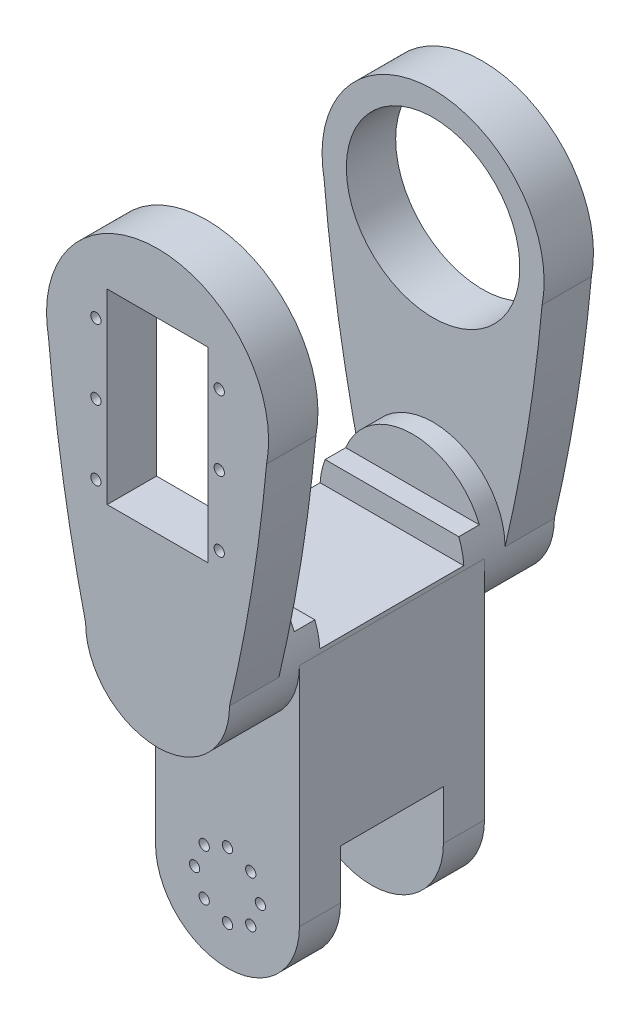
SolidWorks part; units mm, degrees
ref_plane "Front Plane" through (0, 0, 0) normal (0, 0, 1) x (1, 0, 0)
ref_plane "Top Plane" through (0, 0, 0) normal (0, 1, 0) x (1, 0, 0)
ref_plane "Right Plane" through (0, 0, 0) normal (1, 0, 0) x (0, 0, -1)
sketch "Sketch2" plane through (0, 0, 0) normal (0, 0, 1) x (1, 0, 0)
  line L0 (-17.5, -27.5) -> (17.5, -27.5)
  line L1 (17.5, -27.5) -> (-17.5, -27.5)
  line L2 (17.5, -27.5) -> (17.5, 27.5)
  line L3 (17.5, 27.5) -> (-17.5, 27.5)
  line L4 (-17.5, -27.5) -> (-17.5, 27.5)
  line L5 (0, 27.5) -> (0, -27.5) construction
  line L6 (17.5, 0) -> (-17.5, 0) construction
  arc A0 (17.5, -27.5) -> (-17.5, -27.5) centre (0, -27.5) cw
  arc A1 (-17.5, 27.5) -> (17.5, 27.5) centre (0, 27.5) cw
  point P0 (0, 0)
  dimension "D1" = 55
  dimension "D2" = 35
extrude "Boss-Extrude1" add sketch "Sketch2" along normal blind 45 contours A1 L3 | L4 L0 L2 L3 | A0 L0
sketch "Sketch5" plane through (0, 0, 45) normal (0, 0, 1) x (1, 0, 0)
  arc A0 (17.5, 27.5) -> (-17.5, 27.5) centre (0, 27.5) ccw
  arc A1 (-17.5, 27.5) -> (17.5, 27.5) centre (0, 27.5) ccw
extrude "Boss-Extrude2" add sketch "Sketch5" along normal blind 5
sketch "Sketch6" plane through (0, 0, 50) normal (0, 0, 1) x (1, 0, 0)
  line L0 (17.5, 67.5) -> (17.5, 27.5)
  line L1 (-17.5, 27.5) -> (-17.5, 67.5)
  line L2 (-17.5, 67.5) -> (17.5, 67.5)
  arc A0 (17.5, 27.5) -> (-17.5, 27.5) centre (0, 27.5) cw
  arc A1 (17.5, 67.5) -> (-17.5, 67.5) centre (0, 67.5) ccw
  circle M2 centre (0, 27.5) radius 17.5
  dimension "50" = 40
extrude "Boss-Extrude3" add sketch "Sketch6" along normal blind 12 contours L2 A1 | L2 L1 L0 M2 | M2
sketch "Sketch7" plane through (0, 0, 0) normal (0, 0, -1) x (-1, 0, 0)
  arc A0 (17.5, 27.5) -> (-17.5, 27.5) centre (0, 27.5) cw
  arc A1 (-17.5, 27.5) -> (17.5, 27.5) centre (0, 27.5) cw
extrude "Boss-Extrude4" add sketch "Sketch7" along normal blind 5
sketch "Sketch8" plane through (0, 0, -5) normal (0, 0, -1) x (-1, 0, 0)
  line L0 (17.5, 27.5) -> (17.5, 67.5)
  line L1 (17.5, 67.5) -> (-17.5, 67.5)
  line L2 (-17.5, 67.5) -> (-17.5, 27.5)
  arc A0 (-17.5, 27.5) -> (17.5, 27.5) centre (0, 27.5) ccw
  arc A1 (17.5, 67.5) -> (-17.5, 67.5) centre (0, 67.5) ccw
  circle M5 centre (0, 27.5) radius 17.5
extrude "Boss-Extrude5" add sketch "Sketch8" along normal blind 12 contours L1 A1 | L1 L2 L0 M5 | M5
sketch "Sketch11" plane through (0, 0, 62) normal (0, 0, 1) x (1, 0, 0)
  line L2 (-17.5, 67.5) -> (-17.5, 27.5)
  line L3 (17.5, 27.5) -> (17.5, 67.5)
  line L4 (-17.5, 67.5) -> (-17.5, 27.5)
  line L5 (17.5, 27.5) -> (17.5, 67.5)
  arc A0 (-17.5, 67.5) -> (17.5, 67.5) centre (0, 88.0609) cw
  arc A3 (17.5, 67.5) -> (-17.5, 67.5) centre (0, 67.5) ccw
  arc A4 (-17.5, 27.5) -> (17.5, 27.5) centre (0, 27.5) ccw
  arc A6 (-17.5, 27.5) -> (17.5, 27.5) centre (0, 27.5) ccw
  dimension "D2" = 27
  dimension "D1" = 0
extrude "Boss-Extrude6" add sketch "Sketch11" against normal blind 12
sketch "Sketch12" plane through (0, 0, -17) normal (0, 0, -1) x (-1, 0, 0)
  line L2 (-17.5, 67.5) -> (-17.5, 27.5)
  line L3 (17.5, 27.5) -> (17.5, 67.5)
  arc A1 (17.5, 67.5) -> (-17.5, 67.5) centre (0, 88.0609) ccw
  arc A3 (17.5, 67.5) -> (-17.5, 67.5) centre (0, 67.5) ccw
  arc A4 (-17.5, 27.5) -> (17.5, 27.5) centre (0, 27.5) ccw
  arc A5 (17.5, 67.5) -> (-17.5, 67.5) centre (0, 67.5) ccw
  dimension "D2" = 27
  dimension "D1" = 0
extrude "Boss-Extrude7" add sketch "Sketch12" against normal blind 12
sketch "Sketch14" plane through (0, 0, 62) normal (0, 0, 1) x (1, 0, 0)
  line L1 (-12.25, 100.4109) -> (12.25, 100.4109)
  line L2 (-12.25, 100.4109) -> (-12.25, 55.0109)
  line L3 (-12.25, 55.0109) -> (12.25, 55.0109)
  line L4 (12.25, 100.4109) -> (12.25, 55.0109)
  line L5 (0, 55.0109) -> (0, 100.4109) construction
  line L6 (-12.25, 77.7109) -> (12.25, 77.7109) construction
  circle A0 centre (0, 88.0609) radius 2.4499
  point P0 (0, 77.7109)
  point P4 (0, 88.0609)
  dimension "D1" = 24.5
  dimension "D2" = 12.35
  dimension "D4" = 45.4
extrude "Cut-Extrude3" cut sketch "Sketch14" against normal blind 12 contours A0 | L4 L1 L2 L3 A0
sketch "Sketch15" plane through (0, 0, -17) normal (0, 0, -1) x (-1, 0, 0)
  circle A0 centre (0, 88.0609) radius 21.1
  dimension "D1" = 42.2
extrude "Cut-Extrude4" cut sketch "Sketch15" against normal blind 12
sketch "Sketch17" plane through (-17.5, 0, 0) normal (-1, 0, 0) x (0, 0, 1)
  line L0 (22.5, -27.5) -> (35, -27.5)
  line L1 (45, -27.5) -> (0, -27.5) construction
  line L2 (22.5, -27.5) -> (10, -27.5)
  line L3 (10, -27.5) -> (10, -45)
  line L4 (0, -45) -> (45, -45) construction
  line L5 (10, -45) -> (35, -45)
  line L6 (35, -45) -> (35, -27.5)
  line L7 (35, -27.5) -> (34.9842, -25.1645)
  line L8 (35, -27.5) -> (35, -15.5)
  line L9 (10, -27.5) -> (10, -15.5)
  line L10 (10, -15.5) -> (35, -15.5)
  dimension "D1" = 12.5
  dimension "12,5" = 12.5
  dimension "D2" = 12
extrude "Cut-Extrude5" cut sketch "Sketch17" against normal through all
sketch "Sketch21" plane through (0, 0, 45) normal (0, 0, 1) x (1, 0, 0)
  circle A9 centre (8, -27.5) radius 1.25
  circle A10 centre (5.6569, -33.1569) radius 1.25
  circle A11 centre (0, -35.5) radius 1.25
  circle A12 centre (-5.6569, -33.1569) radius 1.25
  circle A13 centre (-8, -27.5) radius 1.25
  circle A14 centre (-5.6569, -21.8431) radius 1.25
  circle A15 centre (0, -19.5) radius 1.25
  circle A16 centre (5.6569, -21.8431) radius 1.25
  point P0 (0, -27.5)
  point P3 (0, -32.5)
  point P21 (0, -32.5)
  point P24 (0, -27.5)
  dimension "D1" = 2.5
  dimension "D2" = 8
  dimension "D3" = 8
extrude "Cut-Extrude7" cut sketch "Sketch21" against normal blind 12
sketch "Sketch23" plane through (0, 0, 0) normal (0, 0, -1) x (-1, 0, 0)
  circle A0 centre (0, -27.5) radius 10.1
  dimension "D1" = 20.2
extrude "Boss-Extrude8" add sketch "Sketch23" along normal blind 6
sketch "Sketch24" plane through (0, 0, -6) normal (0, 0, -1) x (-1, 0, 0)
  circle A0 centre (0, -27.5) radius 8.5
  dimension "D1" = 17
extrude "Cut-Extrude8" cut sketch "Sketch24" against normal blind 6
sketch "Sketch25" plane through (0, 0, 0) normal (0, 0, -1) x (-1, 0, 0)
  circle A0 centre (0, -27.5) radius 2.7
  dimension "D1" = 5.4
extrude "Cut-Extrude9" cut sketch "Sketch25" against normal blind 18
sketch "Sketch26" plane through (0, 0, 62) normal (0, 0, 1) x (1, 0, 0)
  arc A0 (26.9918, 88.7245) -> (17.5, 27.5) centre (-371.8448, 119.2095) cw
  arc A3 (17.5, 67.5) -> (-17.5, 67.5) centre (0, 88.0609) ccw construction
  arc A4 (-26.9918, 88.7245) -> (-17.5, 27.5) centre (371.8448, 119.2095) ccw
  line M5 (17.5, 27.5) -> (17.5, 67.5)
  arc M6 (17.5, 67.5) -> (-17.5, 67.5) centre (0, 88.0609) ccw
  line M7 (-17.5, 67.5) -> (-17.5, 27.5)
extrude "Boss-Extrude9" add sketch "Sketch26" against normal blind 12 contours A4 M6 M7 | A0 M6 M5
sketch "Sketch30" plane through (0, 0, 62) normal (0, 0, 1) x (1, 0, 0)
  line L0 (12.25, 100.4109) -> (-12.25, 100.4109) construction
  line L1 (12.25, 55.0109) -> (12.25, 100.4109) construction
  line L2 (0, 100.4109) -> (0, 88.0609)
  circle A0 centre (15, 92.9109) radius 1.25
  circle A1 centre (15, 75.9109) radius 1.25
  circle A2 centre (15, 58.9109) radius 1.25
  circle A3 centre (-15, 92.9109) radius 1.25
  circle A4 centre (-15, 75.9109) radius 1.25
  circle A5 centre (-15, 58.9109) radius 1.25
  point P8 (15, 58.9109)
  dimension "D2" = 2.5
  dimension "D1" = 2.75
  dimension "7,5" = 7.5
  dimension "D3" = 3
extrude "Cut-Extrude11" cut sketch "Sketch30" against normal blind 12 contours A0 | A3 | A4 | A1 | A2 | A5
sketch "Sketch31" plane through (0, 0, 50) normal (0, 0, -1) x (-1, 0, 0)
  line L0 (0, 100.4109) -> (0, 89.0564)
  line L1 (-12.25, 100.4109) -> (12.25, 100.4109) construction
  circle A0 centre (15, 92.9109) radius 2
  circle A1 centre (15, 75.9109) radius 2
  circle A2 centre (15, 58.9109) radius 2
  circle A3 centre (-15, 58.9109) radius 2
  circle A4 centre (-15, 75.9109) radius 2
  circle A5 centre (-15, 92.9109) radius 2
  dimension "D1" = 4
  dimension "D2" = 3
extrude "Cut-Extrude12" cut sketch "Sketch31" against normal blind 2.5 contours A0 | A1 | A2 | A3 | A4 | A5
sketch "Sketch32" plane through (0, 0, -17) normal (0, 0, -1) x (-1, 0, 0)
  arc A0 (26.9918, 88.7245) -> (17.5, 27.5) centre (-371.8448, 119.2095) cw
  arc A1 (17.5, 67.5) -> (-17.5, 67.5) centre (0, 88.0609) ccw construction
  arc A2 (-26.9918, 88.7245) -> (-17.5, 27.5) centre (371.8448, 119.2095) ccw
  line M2 (17.5, 27.5) -> (17.5, 67.5)
  arc M3 (17.5, 67.5) -> (-17.5, 67.5) centre (0, 88.0609) ccw
  line M4 (-17.5, 67.5) -> (-17.5, 27.5)
extrude "Boss-Extrude11" add sketch "Sketch32" against normal blind 12 contours A2 M3 M4 | A0 M3 M2
sketch "Sketch33" plane through (-17.5, 0, 0) normal (-1, 0, 0) x (0, 0, 1)
  line L0 (45, 34) -> (0, 34)
  line L1 (0, 34) -> (0, 45)
  line L2 (50, 45) -> (-5, 45) construction
  line L3 (45, 45) -> (45, 34)
  line L4 (45, 45) -> (0, 45)
  line L5 (45, 27.5) -> (0, 27.5) construction
  line L6 (22.5, 34) -> (22.5, 28.5)
  line L7 (22.5, 28.5) -> (40, 28.5)
  line L8 (22.5, 28.5) -> (5, 28.5)
  line L9 (5, 28.5) -> (5, 34)
  line L10 (40, 28.5) -> (40, 34)
  line L11 (40, 34) -> (5, 34)
  point P7 (22.5, 34)
  point P10 (22.5, 27.5)
  dimension "D1" = 11
  dimension "D2" = 0
  dimension "D3" = 17.5
  dimension "D4" = 17.5
  dimension "D5" = 5.5
extrude "Cut-Extrude13" cut sketch "Sketch33" against normal blind 40 contours L9 L8 L6 L0 | L7 L10 L0 L6 | L3 L4 L1 L0
